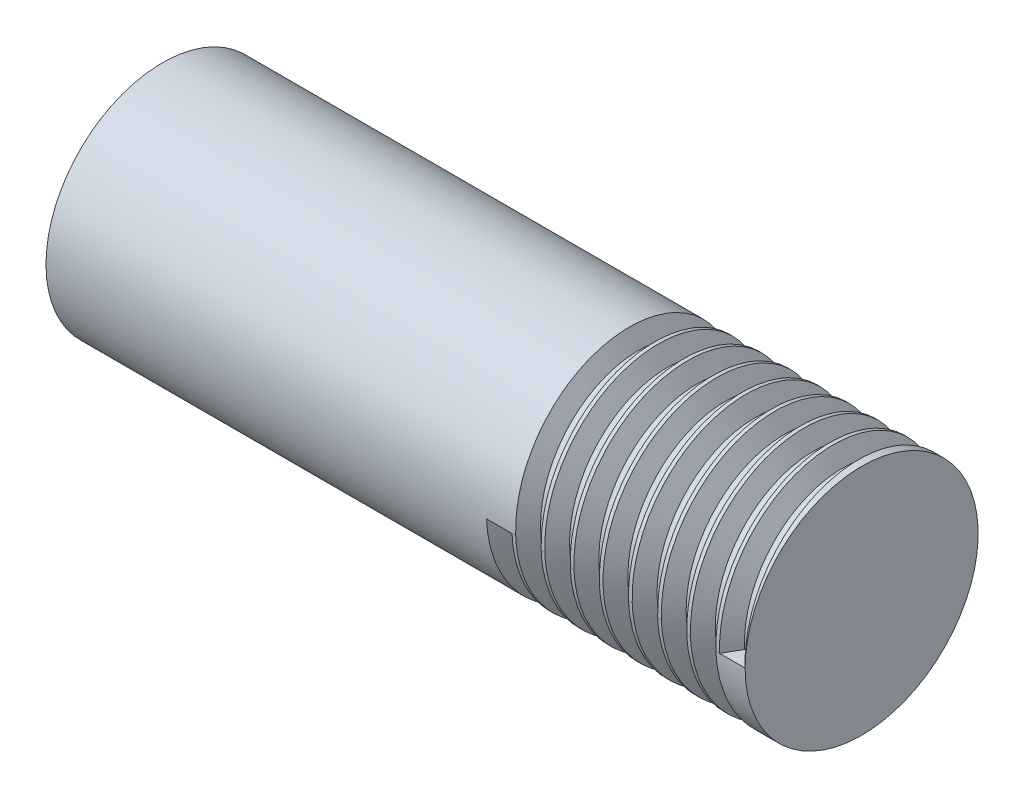
SolidWorks part; units mm, degrees
ref_plane "Front Plane" through (0, 0, 0) normal (0, 0, 1) x (1, 0, 0)
ref_plane "Top Plane" through (0, 0, 0) normal (0, 1, 0) x (1, 0, 0)
ref_plane "Right Plane" through (0, 0, 0) normal (1, 0, 0) x (0, 0, -1)
sketch "Sketch1" plane through (0, 0, 0) normal (1, 0, 0) x (0, 0, -1)
  circle A0 centre (0, 0) radius 5
extrude "Boss-Extrude1" add sketch "Sketch1" along normal blind 30
thread "Thread1" pitch 1.25 method cut profile "Thread Profile1" start angle 0, offset 0, length 10, pitch 1.25, diameter 10
ref_plane "Plane1" through (30, 0, 5) normal (0, -1, 0) x (0, 0, 1)
sketch "Thread Profile1" plane through (30, 0, 5) normal (0, -1, 0) x (0, 0, 1)
  line L0 (0, 0) -> (0, 1.25) construction
  line L11 (0, 0) -> (0, 1.0937)
  line L12 (0, 1.0937) -> (-0.6766, 0.7031)
  line L13 (-0.6766, 0.7031) -> (-0.6766, 0.3906)
  line L15 (-0.6766, 0.3906) -> (0, 0)
  line L17 (-0.6766, 0.5469) -> (0, 0.5469) construction
  point P2 (0, 0)
  dimension "Pitch" = 1.25
  dimension "Profile_Angle" = 60
  dimension "Profile_Land" = 0.3125
  dimension "Profile_Height" = 0.6766
sketch "Sketch2" plane through (30, 0, 0) normal (1, 0, 0) x (0, 0, -1)
  circle A0 centre (0, 0) radius 4.2691
